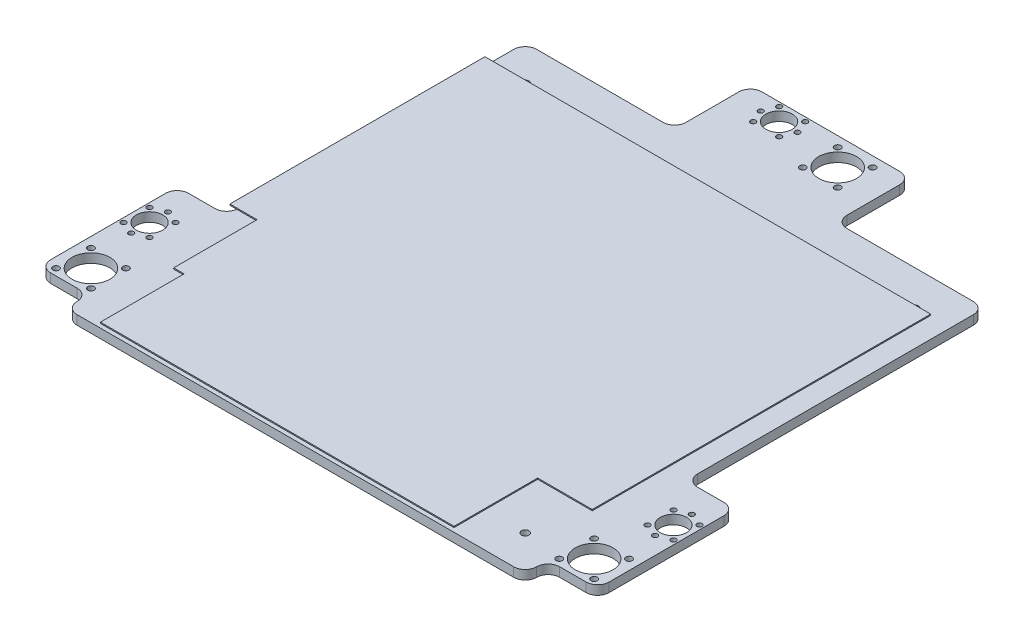
SolidWorks part; units mm, degrees
material "Plain Carbon Steel"
ref_plane "Front Plane" through (0, 0, 0) normal (0, 0, 1) x (1, 0, 0)
ref_plane "Top Plane" through (0, 0, 0) normal (0, 1, 0) x (1, 0, 0)
ref_plane "Right Plane" through (0, 0, 0) normal (1, 0, 0) x (0, 0, -1)
sketch "Sketch1" plane through (0, 0, 0) normal (0, 1, 0) x (1, 0, 0)
  line L0 (-243, -200) -> (243, -200)
  line L1 (-169.5, 169.5) -> (169.5, 169.5)
  line L2 (-169.5, 169.5) -> (-169.5, -169.5)
  line L3 (-169.5, -169.5) -> (169.5, -169.5)
  line L4 (169.5, 169.5) -> (169.5, -169.5)
  line L5 (-169.5, 169.5) -> (169.5, -169.5) construction
  line L6 (-169.5, -169.5) -> (169.5, 169.5) construction
  line L7 (-243, -200) -> (-243, 246)
  line L8 (-243, 246) -> (243, 246)
  line L9 (243, 246) -> (243, -200)
  line L10 (0, 0) -> (0, -200)
  point P0 (0, 0)
  dimension "D1" = 339
  dimension "D2" = 446
  dimension "D3" = 486
  dimension "D4" = 200
sketch "Sketch2" plane through (0, 0, 0) normal (0, 1, 0) x (1, 0, 0)
  line L0 (243, 246) -> (243, -200) construction
  line L1 (-243, 246) -> (243, 246) construction
  line L2 (-243, -200) -> (-243, 246) construction
  line L3 (-243, -200) -> (243, -200) construction
  line L4 (243, 246) -> (243, -200)
  line L5 (-243, 246) -> (243, 246)
  line L6 (-243, -200) -> (-243, 246)
  line L7 (-243, -200) -> (243, -200)
extrude "Boss-Extrude1" add sketch "Sketch2" along normal blind 8
sketch "Sketch3" plane through (0, 8, 0) normal (0, 1, 0) x (1, 0, 0)
  circle A0 centre (-203.7972, -194.2028) radius 2.75 construction
  circle A1 centre (-234.2028, -194.2028) radius 2.75 construction
  circle A2 centre (-234.2028, -163.7972) radius 2.75 construction
  circle A3 centre (-203.7972, -163.7972) radius 2.75 construction
  circle A4 centre (-203.7972, -194.2028) radius 2.75
  circle A5 centre (-234.2028, -194.2028) radius 2.75
  circle A6 centre (-234.2028, -163.7972) radius 2.75
  circle A7 centre (-203.7972, -163.7972) radius 2.75
  circle A8 centre (-239.3137, -107.6863) radius 2.35 construction
  circle A9 centre (-239.3137, -107.6863) radius 2.35 construction
  circle A10 centre (-239.3137, -130.3137) radius 2.35 construction
  circle A11 centre (-239.3137, -130.3137) radius 2.35 construction
  circle A12 centre (-228, -135) radius 2.35 construction
  circle A13 centre (-228, -135) radius 2.35 construction
  circle A14 centre (-216.6863, -130.3137) radius 2.35 construction
  circle A15 centre (-216.6863, -130.3137) radius 2.35 construction
  circle A16 centre (-216.6863, -107.6863) radius 2.35 construction
  circle A17 centre (-216.6863, -107.6863) radius 2.35 construction
  circle A18 centre (-228, -103) radius 2.35 construction
  circle A19 centre (-228, -103) radius 2.35 construction
  circle A20 centre (-239.3137, -107.6863) radius 2.35
  circle A21 centre (-239.3137, -107.6863) radius 2.35
  circle A22 centre (-239.3137, -130.3137) radius 2.35
  circle A23 centre (-239.3137, -130.3137) radius 2.35
  circle A24 centre (-228, -135) radius 2.35
  circle A25 centre (-228, -135) radius 2.35
  circle A26 centre (-216.6863, -130.3137) radius 2.35
  circle A27 centre (-216.6863, -130.3137) radius 2.35
  circle A28 centre (-216.6863, -107.6863) radius 2.35
  circle A29 centre (-216.6863, -107.6863) radius 2.35
  circle A30 centre (-228, -103) radius 2.35
  circle A31 centre (-228, -103) radius 2.35
  circle A32 centre (-228, -119) radius 11 construction
  circle A33 centre (-219, -179) radius 16 construction
  circle A34 centre (-228, -119) radius 11
  circle A35 centre (-219, -179) radius 16
  circle A36 centre (-18.6863, 242.3137) radius 2.35 construction
  circle A37 centre (-18.6863, 242.3137) radius 2.35 construction
  circle A38 centre (-41.3137, 242.3137) radius 2.35 construction
  circle A39 centre (-41.3137, 242.3137) radius 2.35 construction
  circle A40 centre (-46, 231) radius 2.35 construction
  circle A41 centre (-46, 231) radius 2.35 construction
  circle A42 centre (-41.3137, 219.6863) radius 2.35 construction
  circle A43 centre (-41.3137, 219.6863) radius 2.35 construction
  circle A44 centre (-18.6863, 219.6863) radius 2.35 construction
  circle A45 centre (-18.6863, 219.6863) radius 2.35 construction
  circle A46 centre (-14, 231) radius 2.35 construction
  circle A47 centre (-14, 231) radius 2.35 construction
  circle A48 centre (-18.6863, 242.3137) radius 2.35
  circle A49 centre (-18.6863, 242.3137) radius 2.35
  circle A50 centre (-41.3137, 242.3137) radius 2.35
  circle A51 centre (-41.3137, 242.3137) radius 2.35
  circle A52 centre (-46, 231) radius 2.35
  circle A53 centre (-46, 231) radius 2.35
  circle A54 centre (-41.3137, 219.6863) radius 2.35
  circle A55 centre (-41.3137, 219.6863) radius 2.35
  circle A56 centre (-18.6863, 219.6863) radius 2.35
  circle A57 centre (-18.6863, 219.6863) radius 2.35
  circle A58 centre (-14, 231) radius 2.35
  circle A59 centre (-14, 231) radius 2.35
  circle A60 centre (-30, 231) radius 11 construction
  circle A61 centre (30, 222) radius 16 construction
  circle A62 centre (45.2028, 237.2028) radius 2.75 construction
  circle A63 centre (14.7972, 237.2028) radius 2.75 construction
  circle A64 centre (14.7972, 206.7972) radius 2.75 construction
  circle A65 centre (45.2028, 206.7972) radius 2.75 construction
  circle A66 centre (-30, 231) radius 11
  circle A67 centre (30, 222) radius 16
  circle A68 centre (45.2028, 237.2028) radius 2.75
  circle A69 centre (14.7972, 237.2028) radius 2.75
  circle A70 centre (14.7972, 206.7972) radius 2.75
  circle A71 centre (45.2028, 206.7972) radius 2.75
hole_wizard "M5 Clearance Hole1" positions "Sketch4" profile "Sketch5" hole size "M5" standard "ANSI Metric" end condition through all
sketch "Sketch4" plane through (0, 8, 0) normal (0, 1, 0) x (1, 0, 0)
  point P0 (-234.2028, -163.7972)
  point P3 (-203.7972, -163.7972)
  point P6 (-203.7972, -194.2028)
  point P9 (-234.2028, -194.2028)
sketch "Sketch5" plane through (-234.2028, 8, 163.7972) normal (1, 0, 0) x (0, 0, 1)
  line L0 (0, 0) -> (0, 8)
  line L1 (0, 8) -> (2.75, 8)
  line L2 (2.75, 8) -> (2.75, 0)
  line L5 (2.75, 0) -> (0, 0)
  line L11 (0, -6.35) -> (0, 107.95) construction
  dimension "Thru Hole Dia." = 5.5
  dimension "Thru Hole Depth" = 8
hole_wizard "M4 Clearance Hole1" positions "Sketch6" profile "Sketch7" hole size "M4" standard "ANSI Metric" end condition through all
sketch "Sketch6" plane through (0, 8, 0) normal (0, 1, 0) x (1, 0, 0)
  point P0 (-228, -135)
  point P3 (-216.6863, -130.3137)
  point P6 (-216.6863, -107.6863)
  point P9 (-228, -103)
  point P12 (-239.3137, -107.6863)
  point P15 (-239.3137, -130.3137)
sketch "Sketch7" plane through (-228, 8, 135) normal (1, 0, 0) x (0, 0, 1)
  line L0 (0, 0) -> (0, 8)
  line L1 (0, 8) -> (2.25, 8)
  line L2 (2.25, 8) -> (2.25, 0)
  line L5 (2.25, 0) -> (0, 0)
  line L11 (0, -6.35) -> (0, 107.95) construction
  dimension "Thru Hole Dia." = 4.5
  dimension "Thru Hole Depth" = 8
sketch "Sketch8" plane through (0, 8, 0) normal (0, 1, 0) x (1, 0, 0)
  circle A0 centre (-228, -119) radius 11.5
  circle A1 centre (-219, -179) radius 16.5
  circle A2 centre (-219, -179) radius 16 construction
  circle A3 centre (-228, -119) radius 11 construction
  dimension "D1" = 0.5
  dimension "D2" = 0.5
extrude "Cut-Extrude1" cut sketch "Sketch8" against normal through all
mirror "Mirror1" about plane through (0, 0, 0) normal (1, 0, 0) of "Cut-Extrude1", "M4 Clearance Hole1", "M5 Clearance Hole1"
hole_wizard "M5 Clearance Hole2" positions "Sketch9" profile "Sketch10" hole size "M5" standard "ANSI Metric" end condition through all
sketch "Sketch9" plane through (0, 8, 0) normal (0, 1, 0) x (1, 0, 0)
  point P0 (45.2028, 206.7972)
  point P3 (14.7972, 206.7972)
  point P6 (14.7972, 237.2028)
  point P9 (45.2028, 237.2028)
sketch "Sketch10" plane through (45.2028, 8, -206.7972) normal (1, 0, 0) x (0, 0, 1)
  line L0 (0, 0) -> (0, 8)
  line L1 (0, 8) -> (2.75, 8)
  line L2 (2.75, 8) -> (2.75, 0)
  line L5 (2.75, 0) -> (0, 0)
  line L11 (0, -6.35) -> (0, 107.95) construction
  dimension "Thru Hole Dia." = 5.5
  dimension "Thru Hole Depth" = 8
hole_wizard "M4 Clearance Hole2" positions "Sketch11" profile "Sketch12" hole size "M4" standard "ANSI Metric" end condition through all
sketch "Sketch11" plane through (0, 8, 0) normal (0, 1, 0) x (1, 0, 0)
  point P0 (-41.3137, 219.6863)
  point P3 (-46, 231)
  point P6 (-41.3137, 242.3137)
  point P9 (-18.6863, 242.3137)
  point P12 (-14, 231)
  point P15 (-18.6863, 219.6863)
sketch "Sketch12" plane through (-41.3137, 8, -219.6863) normal (1, 0, 0) x (0, 0, 1)
  line L0 (0, 0) -> (0, 8)
  line L1 (0, 8) -> (2.25, 8)
  line L2 (2.25, 8) -> (2.25, 0)
  line L5 (2.25, 0) -> (0, 0)
  line L11 (0, -6.35) -> (0, 107.95) construction
  dimension "Thru Hole Dia." = 4.5
  dimension "Thru Hole Depth" = 8
sketch "Sketch13" plane through (0, 8, 0) normal (0, 1, 0) x (1, 0, 0)
  circle A0 centre (-30, 231) radius 11.5
  circle A1 centre (30, 222) radius 16.5
  circle A3 centre (-228, -119) radius 11.5 construction
  circle A4 centre (-219, -179) radius 16.5 construction
extrude "Cut-Extrude2" cut sketch "Sketch13" against normal through all
sketch "Sketch17" plane through (0, 8, 0) normal (0, 1, 0) x (1, 0, 0)
  line L1 (154.5, 139.5) -> (-154.5, 139.5)
  line L2 (154.5, 139.5) -> (154.5, -139.5)
  line L3 (154.5, -139.5) -> (-154.5, -139.5)
  line L4 (-154.5, 139.5) -> (-154.5, -139.5)
  line L5 (154.5, 139.5) -> (-154.5, -139.5) construction
  line L6 (154.5, -139.5) -> (-154.5, 139.5) construction
  point P0 (0, 0)
  dimension "D1" = 15
  dimension "D2" = 30
extrude "Cut-Extrude3" [suppressed] cut sketch "Sketch17" against normal through all
sketch "Sketch18" plane through (0, 8, 0) normal (0, 1, 0) x (1, 0, 0)
  line L0 (-243, -200) -> (243, -200) construction
  line L1 (-154.5, -200) -> (154.5, -200)
  line L2 (-154.5, -200) -> (-154.5, -169.5)
  line L3 (-154.5, -169.5) -> (154.5, -169.5)
  line L4 (154.5, -200) -> (154.5, -169.5)
  line L5 (-169.5, -169.5) -> (169.5, -169.5) construction
  line L6 (0, -169.5) -> (0, 0) construction
  dimension "D1" = 15
extrude "Cut-Extrude4" [suppressed] cut sketch "Sketch18" against normal through all
sketch "Sketch19" plane through (0, 8, 0) normal (0, 1, 0) x (1, 0, 0)
  line L0 (-243, -80) -> (-200, -80)
  line L1 (-243, 246) -> (-243, -200) construction
  line L2 (-200, -80) -> (-200, 180)
  line L3 (-200, 180) -> (-70, 180)
  line L4 (-70, 180) -> (-70, 246)
  line L5 (243, 246) -> (-243, 246) construction
  line L6 (0, 0) -> (0, -200) construction
  line L7 (-243, -200) -> (243, -200) construction
  line L8 (-243, -80) -> (-243, 246)
  line L9 (-243, 246) -> (-70, 246)
  dimension "D1" = 200
  dimension "D2" = 180
  dimension "D3" = 70
  dimension "D4" = 120
extrude "Cut-Extrude5" cut sketch "Sketch19" against normal through all
mirror "Mirror2" about plane through (0, 0, 0) normal (1, 0, 0) of "Cut-Extrude5"
sketch "Sketch20" plane through (0, 8, 0) normal (0, 1, 0) x (1, 0, 0)
  line L0 (-200, -80) -> (-200, 180) construction
  line L1 (200, 180) -> (-200, 180)
  line L2 (200, 180) -> (200, -220)
  line L3 (200, -220) -> (-200, -220)
  line L4 (-200, 180) -> (-200, -220)
  dimension "D1" = 400
extrude "Boss-Extrude2" add sketch "Sketch20" against normal up to surface (8 mm away) up to face at (-30, 0, -219.5)
fillet "Fillet1" [suppressed] radius 10
fillet "Fillet2" [suppressed] radius 20
fillet "Fillet3" radius 10 16 edges at (-70, 4, -180) (-200, 4, -180) (-200, 4, 80) (70, 4, -180) (200, 4, -180) (200, 4, 80) (-243, 4, 200) (-243, 4, 80) (243, 4, 200) (243, 4, 80) (-70, 4, -246) (70, 4, -246) (200, 4, 220) (200, 4, 200) (-200, 4, 220) (-200, 4, 200)
sketch "Sketch21" plane through (0, 8, 0) normal (0, 1, 0) x (1, 0, 0)
  line L0 (-200, -70) -> (-200, 170) construction
  line L1 (200, -220) -> (-200, -220)
  line L2 (200, -220) -> (200, 180)
  line L3 (200, 180) -> (-200, 180)
  line L4 (-200, -220) -> (-200, 180)
  line L5 (-190, 180) -> (-80, 180) construction
  line L6 (200, -70) -> (200, 170) construction
  line L7 (-190, -220) -> (190, -220) construction
  line L8 (-200, 180) -> (200, -220) construction
  line L10 (169.5, 149.5) -> (-169.5, 149.5)
  line L11 (169.5, 149.5) -> (169.5, -189.5)
  line L12 (169.5, -189.5) -> (-169.5, -189.5)
  line L13 (-169.5, 149.5) -> (-169.5, -189.5)
  line L14 (169.5, 149.5) -> (-169.5, -189.5) construction
  line L15 (169.5, -189.5) -> (-169.5, 149.5) construction
  point P12 (0, -20)
  dimension "D1" = 339
hole_wizard "M6 Clearance Hole1" positions "Sketch15" profile "Sketch16" hole size "M6" standard "ANSI Metric" end condition through all
sketch "Sketch15" plane through (0, 8, 0) normal (0, 1, 0) x (1, 0, 0)
  point P0 (-169.5, -189.5)
  point P2 (-169.5, 149.5)
  point P4 (169.5, 149.5)
  point P6 (169.5, -189.5)
sketch "Sketch16" plane through (-169.5, 8, 189.5) normal (1, 0, 0) x (0, 0, 1)
  line L0 (0, 0) -> (0, 8)
  line L1 (0, 8) -> (3.3, 8)
  line L2 (3.3, 8) -> (3.3, 0)
  line L5 (3.3, 0) -> (0, 0)
  line L11 (0, -6.35) -> (0, 107.95) construction
  dimension "Thru Hole Dia." = 6.6
  dimension "Thru Hole Depth" = 8
sketch "Sketch22" plane through (0, 8, 0) normal (0, 1, 0) x (1, 0, 0)
  line L0 (134.5138, -143.6605) -> (182, -143.6605)
  line L1 (-182.3325, -143.6605) -> (-173.2538, -143.6605)
  line L2 (-182.3325, -143.6605) -> (-182.3325, -71.0816)
  line L5 (-206, 150.9333) -> (182, 150.9333)
  line L6 (-206, 150.9333) -> (-206, -71.0816)
  line L7 (-206, -71.0816) -> (-182.3325, -71.0816)
  line L8 (182, 150.9333) -> (182, -143.6605)
  line L9 (-173.2538, -216.467) -> (134.5138, -216.467)
  line L10 (-173.2538, -216.467) -> (-173.2538, -143.6605)
  line L12 (134.5138, -216.467) -> (134.5138, -143.6605)
  line L15 (190, 180) -> (80, 180) construction
  line L16 (200, -70) -> (200, 170) construction
  point P1 (0, 0)
  point P12 (134.9359, -216.467)
  point P13 (-181.9104, -142.9852)
  point P14 (-205.5779, -63.165)
  point P16 (148.0549, -143.6605)
  point P18 (177.6605, -71.0816)
  point P22 (177.6605, 150.9333)
  point P25 (177.6605, -71.8402)
  point P26 (177.6605, -142.869)
  dimension "D1" = 18
  dimension "D2" = 29.0667
  dimension "D3" = 388
  dimension "D4" = 23.6675
  dimension "D5" = 72.5789
  dimension "D6" = 222.0149
  dimension "D7" = 72.8065
  dimension "D8" = 307.7676
  dimension "D9" = 9.0787
extrude "Boss-Extrude3" add sketch "Sketch22" along normal blind 1 separate body contours L6 L7 L2 L1 L10 L9 L12 L0 L8 L5
